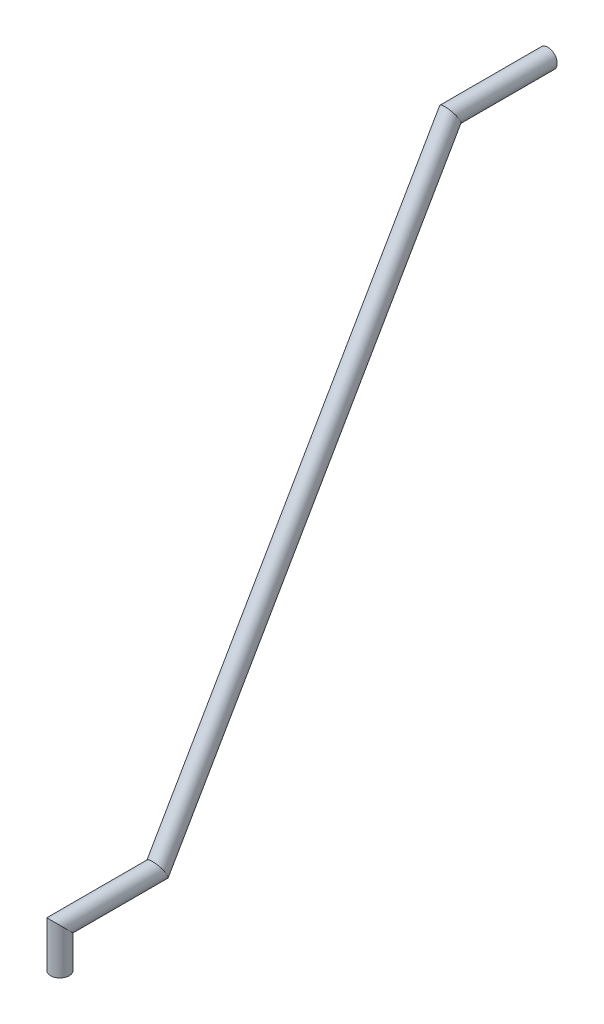
SolidWorks part; units mm, degrees
material "Silicon Rubber"
ref_plane "Front Plane" through (0, 0, 0) normal (0, 0, 1) x (1, 0, 0)
ref_plane "Top Plane" through (0, 0, 0) normal (0, 1, 0) x (1, 0, 0)
ref_plane "Right Plane" through (0, 0, 0) normal (1, 0, 0) x (0, 0, -1)
sketch "Sketch2" plane through (0, 0, 0) normal (0, 1, 0) x (1, 0, 0)
  line L0 (0, 2.5) -> (0, 8) construction
  line L1 (-17.5, 0) -> (17.5, 0) construction
  circle A0 centre (0, 0) radius 17.5 construction
  circle A1 centre (0, 0) radius 2.5 construction
  circle A2 centre (0, 8) radius 3.175
  circle A3 centre (0, 8) radius 4.7625
  circle A4 centre (0, -8) radius 3.175 construction
  circle A5 centre (0, -8) radius 4.7625 construction
  dimension "D1" = 35
  dimension "D2" = 5
  dimension "D4" = 6.35
  dimension "D5" = 9.525
  dimension "D3" = 5.5
sketch "Sketch4" plane through (0, 0, 0) normal (1, 0, 0) x (0, 0, -1)
  line L0 (8, 0) -> (8, 20)
  line L1 (8, 20) -> (58, 20)
  line L2 (58, 20) -> (208, 279.8076)
  line L3 (208, 279.8076) -> (258, 279.8076)
  dimension "D1" = 20
  dimension "D2" = 50
  dimension "D3" = 300
  dimension "D4" = 60
  dimension "D5" = 50
sweep "Sweep2" add profiles "Sketch2" path "Sketch4"
ref_plane "Plane2" through (0, 0, -228) normal (0, 0, -1) x (1, 0, 0)
